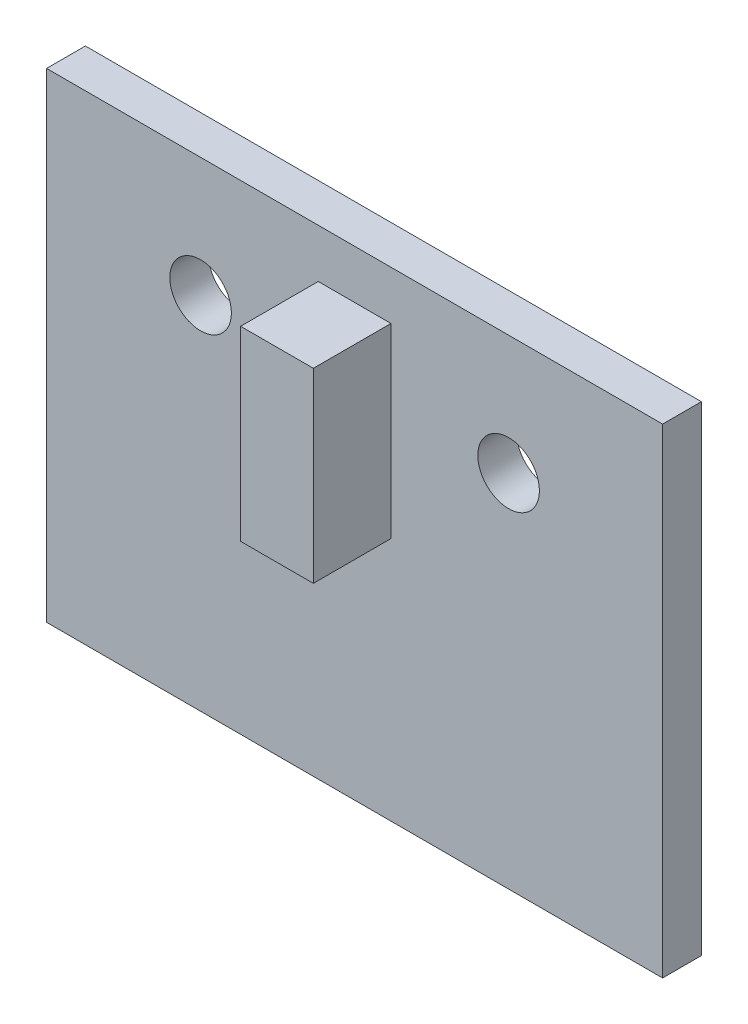
SolidWorks part; units mm, degrees
ref_plane "Front Plane" through (0, 0, 0) normal (0, 0, 1) x (1, 0, 0)
ref_plane "Top Plane" through (0, 0, 0) normal (0, 1, 0) x (1, 0, 0)
ref_plane "Right Plane" through (0, 0, 0) normal (1, 0, 0) x (0, 0, -1)
sketch "Sketch1" plane through (0, 0, 0) normal (0, 0, 1) x (1, 0, 0)
  line L0 (-3.75, 40.295) -> (-31.75, 40.295)
  line L1 (-31.75, 45.315) -> (31.75, 45.315)
  line L2 (-31.75, 45.315) -> (-31.75, -4.135)
  line L3 (-31.75, -4.135) -> (31.75, -4.135)
  line L4 (31.75, 45.315) -> (31.75, -4.135)
  line L5 (3.75, 40.295) -> (31.75, 40.295)
  line L6 (0, 40.295) -> (3.75, 40.295)
  line L8 (0, 21.095) -> (3.75, 21.095)
  line L9 (3.75, 40.295) -> (3.75, 21.095)
  line L10 (0, 21.095) -> (-3.75, 21.095)
  line L12 (0, 40.295) -> (-3.75, 40.295)
  line L13 (-3.75, 21.095) -> (-3.75, 40.295)
  circle A0 centre (-15.875, 33) radius 3.175
  circle A1 centre (15.875, 33) radius 3.175
extrude "Boss-Extrude1" add sketch "Sketch1" along normal blind 4 contours L10 L13 L0 L2 L3 L4 L5 L9 L8 | L12 L6 L5 L4 L1 L2 L0 region at (0, 17.0235, 0) region at (0, 42.805, 0)
extrude "Boss-Extrude2" add sketch "Sketch1<3>" along normal blind 12 separate body contours L13 L10 L8 L9 L6 L12 region at (0, 30.695, 0)
sketch "Sketch1<3>" plane through (0, 0, 0) normal (0, 0, 1) x (1, 0, 0) same geometry as "Sketch1"
